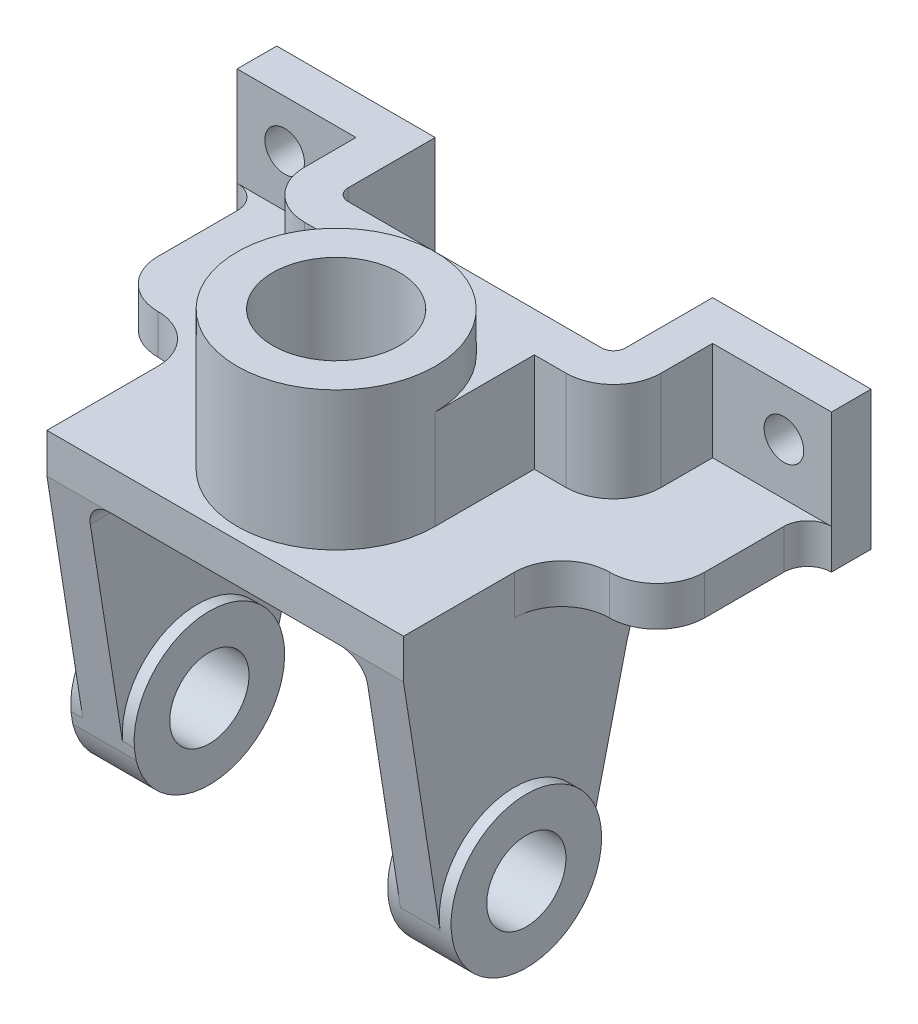
SolidWorks part; units mm, degrees
other "Markup1"
sketch "Sketch6" plane through (75, 35, 0) normal (0.5408, 0.3078, 0.7828) x (0.8301, -0.0444, -0.5559)
ref_plane "Front Plane" through (0, 0, 0) normal (0, 0, 1) x (1, 0, 0)
ref_plane "Top Plane" through (0, 0, 0) normal (0, 1, 0) x (1, 0, 0)
ref_plane "Right Plane" through (0, 0, 0) normal (1, 0, 0) x (0, 0, -1)
sketch "Sketch1" plane through (0, 0, 0) normal (0, 1, 0) x (1, 0, 0)
  line L0 (0, 45) -> (0, -45) construction
  line L1 (-45, 0) -> (45, 0)
  line L2 (-45, 0) -> (-45, 40)
  line L3 (-45, 40) -> (-69, 40)
  line L4 (-69, 40) -> (-69, 72)
  line L5 (-75, 78) -> (75, 78)
  line L6 (45, 0) -> (45, 40)
  line L7 (69, 40) -> (69, 72)
  line L8 (45, 40) -> (69, 40)
  arc A0 (-69, 72) -> (-75, 78) centre (-75, 72) ccw
  arc A1 (69, 72) -> (75, 78) centre (75, 72) cw
  point P4 (0, 0)
  point P7 (0, 0)
  point P18 (0, 78)
  dimension "D4" = 12
  dimension "D1" = 90
  dimension "D2" = 40
  dimension "D3" = 69
  dimension "D5" = 78
extrude "Boss-Extrude1" add sketch "Sketch1" against normal blind 10
sketch "Sketch2" plane through (0, 0, 0) normal (0, 1, 0) x (1, 0, 0)
  line L0 (75, 78) -> (-75, 78) construction
  circle A0 centre (0, 28) radius 25
  circle A1 centre (0, 28) radius 16
  dimension "D2" = 50
  dimension "D3" = 32
  dimension "D1" = 50
extrude "Boss-Extrude2" add sketch "Sketch2" along normal blind 35
sketch "Sketch3" plane through (0, 35, 0) normal (0, 1, 0) x (1, 0, 0)
  line L0 (0, 164.8643) -> (0, -8.8643) construction
  line L2 (32, 63) -> (-32, 63)
  line L3 (75, 78) -> (-75, 78) construction
  line L4 (-25, 28) -> (-25, 53)
  line L5 (-35, 66) -> (-35, 88)
  line L6 (-35, 88) -> (-75, 88)
  line L7 (-75, 88) -> (-75, 78)
  line L8 (-75, 78) -> (-45, 78)
  line L9 (-45, 78) -> (-45, 65)
  line L10 (-33, 53) -> (-25, 53)
  line L11 (33, 53) -> (25, 53)
  line L12 (45, 78) -> (45, 65)
  line L13 (75, 78) -> (45, 78)
  line L14 (75, 88) -> (75, 78)
  line L15 (35, 88) -> (75, 88)
  line L16 (35, 66) -> (35, 88)
  line L17 (25, 28) -> (25, 53)
  circle A0 centre (0, 28) radius 25 construction
  circle A1 centre (0, 28) radius 25 construction
  arc A2 (-32, 63) -> (-35, 66) centre (-32, 66) cw
  arc A3 (-33, 53) -> (-45, 65) centre (-33, 65) cw
  arc A4 (25, 28) -> (-25, 28) centre (0, 28) ccw
  arc A5 (33, 53) -> (45, 65) centre (33, 65) ccw
  arc A6 (32, 63) -> (35, 66) centre (32, 66) ccw
  point P3 (0, 78)
  point P9 (45, 53)
  point P21 (-35, 63)
  point P26 (-45, 53)
  point P28 (-5.9122, 63)
  point P29 (0, 0)
  point P41 (0, 63)
  point P42 (35, 63)
  dimension "D5" = 3
  dimension "D9" = 12
  dimension "D1" = 35
  dimension "D2" = 15
  dimension "D3" = 25
  dimension "D4" = 75
  dimension "D6" = 10
  dimension "D7" = 45
  dimension "D8" = 25
  dimension "D10" = 25
  dimension "D12" = 75
extrude "Boss-Extrude4" add sketch "Sketch3" against normal blind 35 from offset 10 contours L12 A5 L11 L17 A4 L4 L10 A3 L9 L8 L7 L6 L5 A2 L2 A6 L16 L15 L14 L13 offset against normal yes
sketch "Sketch4" plane through (0, 0, -78) normal (0, 0, 1) x (1, 0, 0)
  line L0 (45, -10) -> (69, -10) construction
  circle A0 centre (63, 13) radius 5
  dimension "D1" = 10
  dimension "D2" = 23
  dimension "D3" = 63
extrude "Cut-Extrude1" cut sketch "Sketch4" against normal blind 35
mirror "Mirror1" about plane through (0, 0, 0) normal (1, 0, 0) of "Cut-Extrude1"
fillet "Fillet1" radius 12 2 edges at (-45, -5, -40) (45, -5, -40)
fillet "Fillet2" radius 12 2 edges at (-69, -5, -40) (69, -5, -40)
sketch "Sketch5" plane through (45, 0, 0) normal (1, 0, 0) x (0, 0, -1)
  line L0 (0, -10) -> (28, -10) construction
  line L1 (28, 35) -> (28, -16.8772) construction
  line L2 (53, 35) -> (3, 35) construction
  line L3 (0, -10) -> (9.2287, -68.9392)
  line L4 (46.4739, -70.44) -> (61, -10)
  line L5 (0, -10) -> (61, -10)
  circle A0 centre (28, -66) radius 10
  circle A1 centre (28, -66) radius 19
  line M5 (0, -10) -> (28, -10)
  dimension "D1" = 38
  dimension "D2" = 20
  dimension "D3" = 56
  dimension "D4" = 33
extrude "Boss-Extrude5" add sketch "Sketch5" against normal mid plane 16 from offset 5 separate body contours A1 A0 region at (45, -47.593, -26.5676) offset against normal yes
extrude "Boss-Extrude6" add sketch "Sketch5<3>" against normal blind 10 contours A1 L4 L5 L3 M5 region at (45, -30.3309, -29.7789)
sketch "Sketch5<3>" plane through (45, 0, 0) normal (1, 0, 0) x (0, 0, -1) same geometry as "Sketch5"
fillet "Fillet3" radius 6 1 edges at (35, -10, -30.5)
fillet "Fillet4" radius 25 1 edges at (37, -10, -61)
sketch "Sketch7" plane through (-45, 0, 0) normal (-1, 0, 0) x (0, 0, 1)
  line L0 (-9.5261, -70.44) -> (0, -10)
  line L1 (0, -10) -> (-78, -10)
  line L2 (-78, -10) -> (-70.786, -12.0513)
  line L3 (-70.786, -12.0513) -> (-64.4554, -16)
  line L4 (-64.4554, -16) -> (-59.385, -21.9416)
  line L5 (-59.385, -21.9416) -> (-56.3956, -29.1579)
  line L6 (-56.3956, -29.1579) -> (-46.4739, -70.44)
  line L7 (-46.4739, -70.44) -> (-56.3956, -29.1579) construction
  circle A0 centre (-28, -66) radius 10
  circle A1 centre (-28, -66) radius 19
  arc A2 (-64.4554, -16) -> (-78, -10.1466) centre (-80.7034, -35) ccw construction
  arc A3 (-56.3956, -29.1579) -> (-64.4554, -16) centre (-80.7034, -35) ccw construction
  point P7 (0, 0)
  line M6 (-28, -10) -> (0, -10)
extrude "Boss-Extrude7" add sketch "Sketch7" against normal mid plane 16 from offset 5 separate body contours A1 L0 A0 region at (-45, -84.4626, -28) offset against normal yes
extrude "Boss-Extrude8" add sketch "Sketch7<3>" against normal blind 10 contours A1 L0 L1 L2 L3 L4 L5 L6 M6 region at (-45, -29.7608, -31.0025)
sketch "Sketch7<3>" plane through (-45, 0, 0) normal (-1, 0, 0) x (0, 0, 1) same geometry as "Sketch7"
fillet "Fillet5" radius 6 1 edges at (-35, -10, -39)
